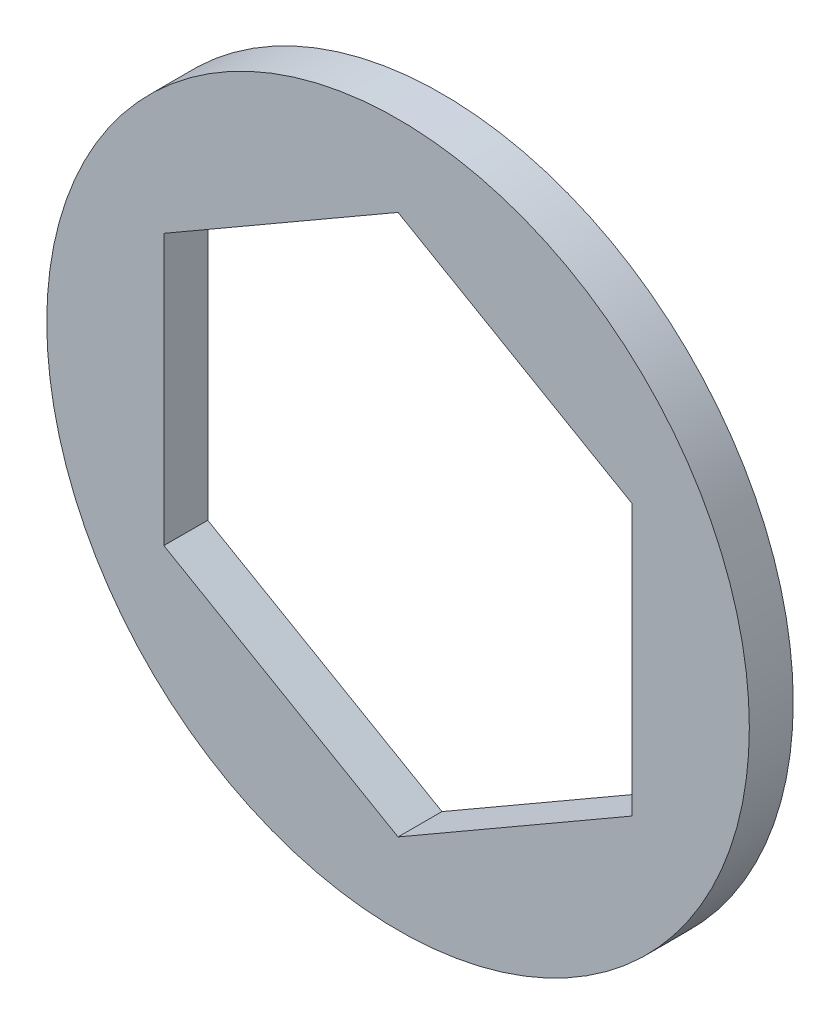
SolidWorks part; units mm, degrees
material "Nylon 101"
ref_plane "Front Plane" through (0, 0, 0) normal (0, 0, 1) x (1, 0, 0)
ref_plane "Top Plane" through (0, 0, 0) normal (0, 1, 0) x (1, 0, 0)
ref_plane "Right Plane" through (0, 0, 0) normal (1, 0, 0) x (0, 0, -1)
sketch "Sketch1" plane through (0, 0, 0) normal (0, 0, 1) x (1, 0, 0)
  line L1 (0, 7.3323) -> (-6.35, 3.6662)
  line L2 (-6.35, 3.6662) -> (-6.35, -3.6662)
  line L3 (-6.35, -3.6662) -> (0, -7.3323)
  line L4 (0, -7.3323) -> (6.35, -3.6662)
  line L5 (6.35, -3.6662) -> (6.35, 3.6662)
  line L6 (6.35, 3.6662) -> (0, 7.3323)
  circle A0 centre (0, 0) radius 9.525
  circle A1 centre (0, 0) radius 6.35 construction
  dimension "D1" = 12.7
  dimension "D2" = 19.05
extrude "Boss-Extrude1" add sketch "Sketch1" along normal blind 1.1906
